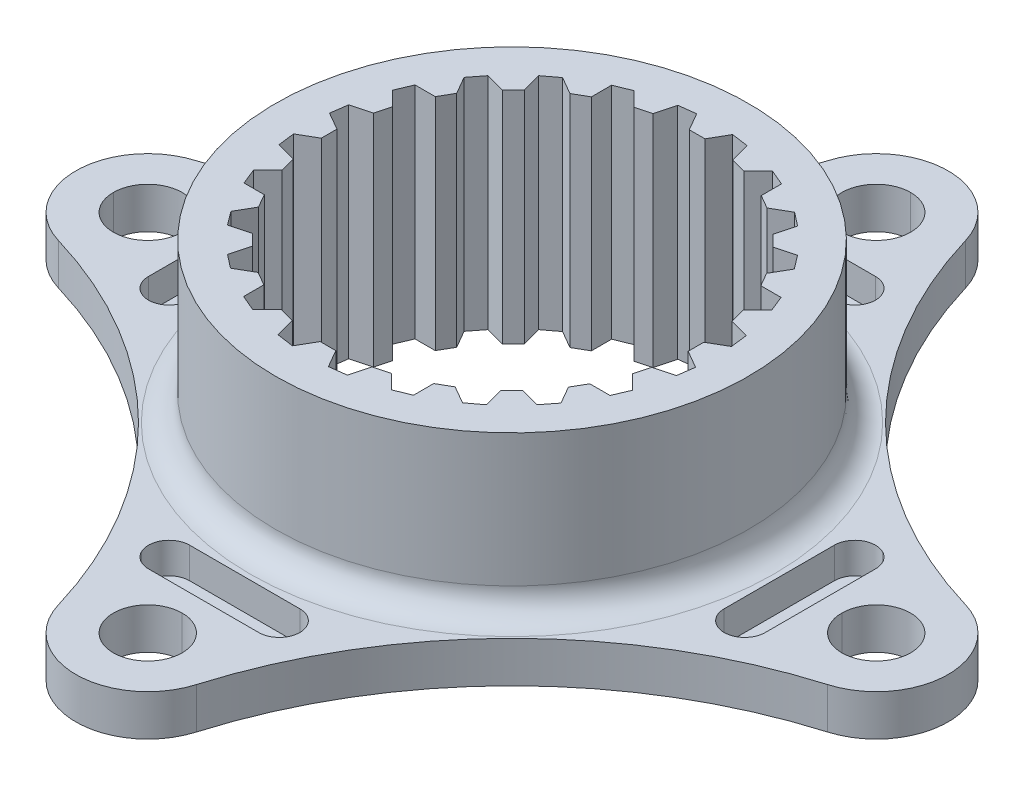
SolidWorks part; units mm, degrees
material "7075-T6 (SN)"
ref_plane "Front Plane" through (0, 0, 0) normal (0, 0, 1) x (1, 0, 0)
ref_plane "Top Plane" through (0, 0, 0) normal (0, 1, 0) x (1, 0, 0)
ref_plane "Right Plane" through (0, 0, 0) normal (1, 0, 0) x (0, 0, -1)
sketch "Sketch1" plane through (0, 0, 0) normal (0, 1, 0) x (1, 0, 0)
  line L0 (274.6284, 454.6081) -> (780.6456, 454.6081) construction
  circle A0 centre (0, 0) radius 23
  dimension "D1" = 46
sketch "Sketch5" plane through (0, 0, 0) normal (0, 1, 0) x (1, 0, 0)
  circle A0 centre (0, 0) radius 23
  circle A1 centre (0, 0) radius 25
  dimension "D1" = 46
  dimension "D2" = 50
sketch "Sketch6" plane through (0, 0, 0) normal (0, 1, 0) x (1, 0, 0)
  line L0 (-0.9689, -22.7363) -> (0.9689, -22.7363)
  line L1 (0.9689, -22.7363) -> (2.2189, -24.9013)
  line L2 (0, 33.3652) -> (0, -36.4848) construction
  line L3 (-0.9689, -22.7363) -> (-2.2189, -24.9013)
  line L4 (-4.9456, -22.1943) -> (-4.2985, -24.6091)
  line L5 (-6.8174, -21.6927) -> (-4.9456, -22.1943)
  line L6 (-6.8174, -21.6927) -> (-8.5852, -23.4605)
  line L7 (-10.5182, -22.6399) -> (-8.5852, -23.4605)
  line L8 (-10.5182, -20.1399) -> (-10.5182, -22.6399)
  line L9 (-12.1965, -19.171) -> (-10.5182, -20.1399)
  line L10 (-12.1965, -19.171) -> (-14.3615, -20.421)
  line L11 (-16.0164, -19.1281) -> (-14.3615, -20.421)
  line L12 (-15.3693, -16.7133) -> (-16.0164, -19.1281)
  line L13 (-16.7396, -15.343) -> (-15.3693, -16.7133)
  line L14 (-16.7396, -15.343) -> (-19.1544, -15.99)
  line L15 (-20.4182, -14.3129) -> (-19.1544, -15.99)
  line L16 (-19.1682, -12.1478) -> (-20.4182, -14.3129)
  line L17 (-20.1372, -10.4696) -> (-19.1682, -12.1478)
  line L18 (-20.1372, -10.4696) -> (-22.6372, -10.4696)
  line L19 (-23.4239, -8.5225) -> (-22.6372, -10.4696)
  line L20 (-21.6561, -6.7547) -> (-23.4239, -8.5225)
  line L21 (-22.1576, -4.8829) -> (-21.6561, -6.7547)
  line L22 (-22.1576, -4.8829) -> (-24.5725, -4.2358)
  line L23 (-24.8284, -2.1515) -> (-24.5725, -4.2358)
  line L24 (-22.6633, -0.9015) -> (-24.8284, -2.1515)
  line L25 (-22.6633, 1.0364) -> (-22.6633, -0.9015)
  line L26 (-22.6633, 1.0364) -> (-24.8284, 2.2864)
  line L27 (-24.5361, 4.366) -> (-24.8284, 2.2864)
  line L28 (-22.1213, 5.013) -> (-24.5361, 4.366)
  line L29 (-21.6197, 6.8849) -> (-22.1213, 5.013)
  line L30 (-21.6197, 6.8849) -> (-23.3875, 8.6526)
  line L31 (-22.567, 10.5857) -> (-23.3875, 8.6526)
  line L32 (-20.067, 10.5857) -> (-22.567, 10.5857)
  line L33 (-19.098, 12.2639) -> (-20.067, 10.5857)
  line L34 (-19.098, 12.2639) -> (-20.348, 14.429)
  line L35 (-19.0552, 16.0838) -> (-20.348, 14.429)
  line L36 (-16.6403, 15.4368) -> (-19.0552, 16.0838)
  line L37 (-15.27, 16.8071) -> (-16.6403, 15.4368)
  line L38 (-15.27, 16.8071) -> (-15.9171, 19.2219)
  line L39 (-14.24, 20.4857) -> (-15.9171, 19.2219)
  line L40 (-12.0749, 19.2357) -> (-14.24, 20.4857)
  line L41 (-10.3966, 20.2046) -> (-12.0749, 19.2357)
  line L42 (-10.3966, 20.2046) -> (-10.3966, 22.7046)
  line L43 (-8.4496, 23.4913) -> (-10.3966, 22.7046)
  line L44 (-6.6818, 21.7235) -> (-8.4496, 23.4913)
  line L45 (-4.8099, 22.2251) -> (-6.6818, 21.7235)
  line L46 (-4.8099, 22.2251) -> (-4.1629, 24.6399)
  line L47 (-2.0785, 24.8958) -> (-4.1629, 24.6399)
  line L48 (-0.8285, 22.7308) -> (-2.0785, 24.8958)
  line L49 (1.1093, 22.7308) -> (-0.8285, 22.7308)
  line L50 (1.1093, 22.7308) -> (2.3593, 24.8958)
  line L51 (4.4389, 24.6036) -> (2.3593, 24.8958)
  line L52 (5.086, 22.1888) -> (4.4389, 24.6036)
  line L53 (6.9578, 21.6872) -> (5.086, 22.1888)
  line L54 (6.9578, 21.6872) -> (8.7256, 23.455)
  line L55 (10.6586, 22.6344) -> (8.7256, 23.455)
  line L56 (10.6586, 20.1344) -> (10.6586, 22.6344)
  line L57 (12.3369, 19.1655) -> (10.6586, 20.1344)
  line L58 (12.3369, 19.1655) -> (14.5019, 20.4155)
  line L59 (16.1568, 19.1226) -> (14.5019, 20.4155)
  line L60 (15.5097, 16.7078) -> (16.1568, 19.1226)
  line L61 (16.88, 15.3375) -> (15.5097, 16.7078)
  line L62 (16.88, 15.3375) -> (19.2948, 15.9845)
  line L63 (20.5586, 14.3074) -> (19.2948, 15.9845)
  line L64 (19.3086, 12.1424) -> (20.5586, 14.3074)
  line L65 (20.2776, 10.4641) -> (19.3086, 12.1424)
  line L66 (20.2776, 10.4641) -> (22.7776, 10.4641)
  line L67 (23.5643, 8.517) -> (22.7776, 10.4641)
  line L68 (21.7965, 6.7492) -> (23.5643, 8.517)
  line L69 (22.298, 4.8774) -> (21.7965, 6.7492)
  line L70 (22.298, 4.8774) -> (24.7129, 4.2303)
  line L71 (24.9688, 2.146) -> (24.7129, 4.2303)
  line L72 (22.8037, 0.896) -> (24.9688, 2.146)
  line L73 (22.8037, -1.0419) -> (22.8037, 0.896)
  line L74 (22.8037, -1.0419) -> (24.9688, -2.2919)
  line L75 (24.6765, -4.3714) -> (24.9688, -2.2919)
  line L76 (22.2617, -5.0185) -> (24.6765, -4.3714)
  line L77 (21.7601, -6.8903) -> (22.2617, -5.0185)
  line L78 (21.7601, -6.8903) -> (23.5279, -8.6581)
  line L79 (22.7074, -10.5912) -> (23.5279, -8.6581)
  line L80 (20.2074, -10.5912) -> (22.7074, -10.5912)
  line L81 (19.2384, -12.2694) -> (20.2074, -10.5912)
  line L82 (19.2384, -12.2694) -> (20.4884, -14.4345)
  line L83 (19.1955, -16.0893) -> (20.4884, -14.4345)
  line L84 (16.7807, -15.4423) -> (19.1955, -16.0893)
  line L85 (15.4104, -16.8126) -> (16.7807, -15.4423)
  line L86 (15.4104, -16.8126) -> (16.0575, -19.2274)
  line L87 (14.3804, -20.4912) -> (16.0575, -19.2274)
  line L88 (12.2153, -19.2412) -> (14.3804, -20.4912)
  line L89 (10.537, -20.2101) -> (12.2153, -19.2412)
  line L90 (10.537, -20.2101) -> (10.537, -22.7101)
  line L91 (8.59, -23.4968) -> (10.537, -22.7101)
  line L92 (6.8222, -21.729) -> (8.59, -23.4968)
  line L93 (4.9503, -22.2306) -> (6.8222, -21.729)
  line L94 (4.9503, -22.2306) -> (4.3033, -24.6454)
  line L95 (2.2189, -24.9013) -> (4.3033, -24.6454)
  line L96 (-4.2985, -24.6091) -> (-2.2189, -24.9013)
  circle A0 centre (0, 0) radius 23 construction
  circle A1 centre (0, 0) radius 25 construction
  point P11 (0, -23)
  point P131 (0.0702, -0.0027)
  dimension "D4" = 2.5
  dimension "D1" = 2.1
  dimension "D5" = 112
  dimension "D6" = 120
  dimension "D2" = 1.9379
  dimension "D3" = 24
sketch "Sketch8" plane through (0, 0, 0) normal (0, 1, 0) x (1, 0, 0)
  circle A0 centre (0, 0) radius 100
  dimension "D1" = 200
extrude "Boss-Extrude4" add sketch "Sketch8" along normal blind 24.638 contours A0
extrude "Cut-Extrude1" cut sketch "Sketch6" along normal through all
sketch "Sketch9" plane through (0, 24.638, 0) normal (0, 1, 0) x (1, 0, 0)
  circle A0 centre (0, 0) radius 29.21
  dimension "D1" = 58.42
extrude "Cut-Extrude3" cut sketch "Sketch9" against normal blind 19.558 flip side to cut
sketch "Sketch10" plane through (0, 5.08, 0) normal (0, 1, 0) x (1, 0, 0)
  circle A1 centre (0, 45) radius 4.2545
  circle A4 centre (45, 0) radius 4.2545
  circle A5 centre (0, -45) radius 4.2545
  circle A6 centre (-45, 0) radius 4.2545
  point P11 (0, 0)
  point P28 (0, 0)
  dimension "D1" = 4
  dimension "D2" = 8.509
  dimension "D3" = 45
sketch "Sketch11" plane through (0, 5.08, 0) normal (0, 1, 0) x (1, 0, 0)
  line L2 (0, 45) -> (8.89, 45) construction
  line L3 (0, 45) -> (8.5239, 47.5249) construction
  circle A0 centre (45, 0) radius 8.89
  circle A1 centre (0, -45) radius 8.89
  circle A2 centre (-45, 0) radius 8.89
  arc A3 (8.5239, 47.5249) -> (47.5249, 8.5239) centre (63.9398, 63.9398) ccw
  arc A4 (47.5249, -8.5239) -> (8.5239, -47.5249) centre (63.9398, -63.9398) ccw
  arc A5 (-8.5239, -47.5249) -> (-47.5249, -8.5239) centre (-63.9398, -63.9398) ccw
  arc A6 (-47.5249, 8.5239) -> (-8.5239, 47.5249) centre (-63.9398, 63.9398) ccw
  circle A8 centre (0, 45) radius 8.89
  point P12 (0, 0)
  point P25 (0, 0)
  circle M10 centre (0, 0) radius 100
  dimension "D4" = 4
  dimension "D1" = 4
  dimension "D2" = 17.78
  dimension "D3" = 16.5
extrude "Cut-Extrude6" cut sketch "Sketch11" against normal blind 7.62 contours A8 M10 region at (-97.1716, 5.08, 0)
extrude "Cut-Extrude7" cut sketch "Sketch10" against normal blind 7.62
fillet "Fillet2" radius 3.175 1 edges at (0, 5.08, 29.21)
ref_plane "Plane1" through (0, 0, 0) normal (0, 0, 1) x (1, 0, 0)
ref_plane "Plane2" through (0, 0, 0) normal (-1, 0, 0) x (0, 0, 1)
split line "Split Line1"
split line "Split Line2"
ref_axis "Axis1" through (0, 5.334, 0) along (0, -1, 0)
sketch "Sketch13" plane through (0, 5.08, 0) normal (0, 1, 0) x (1, 0, 0)
  line L0 (0, 2.794) -> (0, -2.794) construction
  line L1 (-8.4262, 38.1) -> (8.4262, 38.1)
  line L2 (-8.4262, 38.1) -> (-10.795, 33.02)
  line L3 (-10.795, 33.02) -> (10.795, 33.02)
  line L4 (8.4262, 38.1) -> (10.795, 33.02)
  point P11 (0, 33.02)
  dimension "D1" = 115
  dimension "D2" = 115
  dimension "D3" = 5.08
  dimension "D4" = 0
  dimension "D5" = 21.59
  dimension "D6" = 33.02
extrude "Cut-Extrude12" cut sketch "Sketch13" against normal blind 3.81 contours L1 L4 L3 L2
fillet "Fillet5" radius 2.54 4 edges at (-10.795, 3.175, -33.02) (10.795, 3.175, -33.02) (-8.4262, 3.175, -38.1) (8.4262, 3.175, -38.1)
pattern_circular "CirPattern1" count 4 over 360 about axis through (0, 5.334, 0) along (0, -1, 0) of "Cut-Extrude12", "Fillet5"
sketch "Sketch14" plane through (0, 0, 0) normal (0, -1, 0) x (1, 0, 0)
  circle A0 centre (0, 0) radius 29.0322
  dimension "D1" = 58.0644
extrude "Boss-Extrude5" add sketch "Sketch14" along normal blind 2.54
extrude "Cut-Extrude17" cut sketch "Sketch6<5>" against normal blind 2.54
sketch "Sketch6<5>" plane through (0, 0, 0) normal (0, 1, 0) x (1, 0, 0) same geometry as "Sketch6"
chamfer "Chamfer1" distance 0.508 angle 45 1 edges at (0, -2.54, -29.0322)
